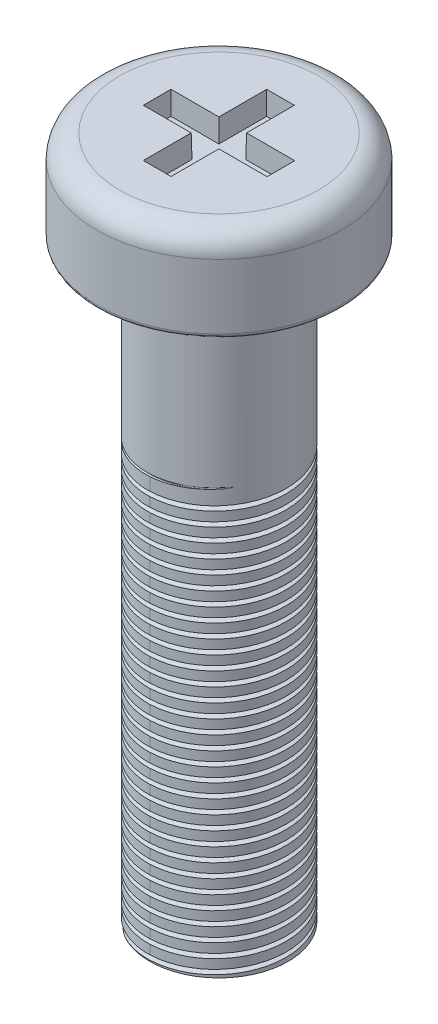
SolidWorks part; units mm, degrees
ref_plane "Front Plane" through (0, 0, 0) normal (0, 0, 1) x (1, 0, 0)
ref_plane "Top Plane" through (0, 0, 0) normal (0, 1, 0) x (1, 0, 0)
ref_plane "Right Plane" through (0, 0, 0) normal (1, 0, 0) x (0, 0, -1)
sketch "Sketch1" plane through (0, 0, 0) normal (0, 1, 0) x (1, 0, 0)
  circle A0 centre (0, 0) radius 2.65
  dimension "D1" = 5.3
extrude "Boss-Extrude1" add sketch "Sketch1" along normal blind 2
sketch "Sketch2" plane through (0, 0, 0) normal (0, -1, 0) x (1, 0, 0)
  circle A0 centre (0, 0) radius 1.5
  dimension "D1" = 3
extrude "Boss-Extrude2" add sketch "Sketch2" along normal blind 12.8
fillet "Fillet1" radius 0.5 1 edges at (0, 2, 2.65)
fillet "Fillet2" radius 0.1 1 edges at (0, 0, 2.65)
sketch "Sketch3" plane through (0, 2, 0) normal (0, 1, 0) x (1, 0, 0)
  line L0 (0.2966, 0.3) -> (1.3407, 0.3)
  line L1 (-1.3407, -0.3) -> (-0.3034, -0.3)
  line L2 (-1.3407, -0.3) -> (-1.3407, 0.3)
  line L3 (-1.3407, 0.3) -> (-0.3034, 0.3)
  line L4 (1.3407, -0.3) -> (1.3407, 0.3)
  line L5 (0.2966, 0.3) -> (0.2966, 1.3361)
  line L6 (-1.3472, 0.3015) -> (-1.3407, 0.3) construction
  line L7 (-0.3034, -1.3361) -> (0.2966, -1.3361)
  line L8 (-0.3034, -1.3361) -> (-0.3034, -0.3)
  line L9 (-0.3034, 1.3361) -> (0.2966, 1.3361)
  line L10 (0.2966, -1.3361) -> (0.2966, -0.3)
  line L11 (-0.0036, -0.0008) -> (-0.0033, 0.0007) construction
  line L12 (-0.0033, 0.0007) -> (-0.003, -0.0007) construction
  line L13 (-0.3034, 0.3) -> (-0.3034, 1.3361)
  line L15 (0.2966, -0.3) -> (1.3407, -0.3)
  line L17 (-0.0036, -0.0008) -> (0, 0) construction
  line L18 (-0.0033, 0.0007) -> (0, 0) construction
  point P0 (0, 0)
  point P6 (-0.0033, 0.0007)
  dimension "D1" = 0.6
  dimension "D2" = 0.6
extrude "Cut-Extrude1" cut sketch "Sketch3" against normal blind 0.5 draft 1
sketch "Sketch4" plane through (0, -12.8, 0) normal (0, -1, 0) x (1, 0, 0)
  circle A1 centre (0, 0) radius 1.5
  circle A2 centre (0, 0) radius 1.5
  dimension "D1" = 0
curve "Helix/Spiral1" pitch 0.3 height 9 turns 30
sketch "Sketch5" plane through (0, 0, 0) normal (0, 0, 1) x (1, 0, 0)
  line L0 (-1.5, -12.85) -> (-1.5, -12.75)
  line L2 (-1.5, 0) -> (-1.5, -12.8) construction
  line L3 (-1.5, -12.75) -> (-1.3951, -12.7858)
  line L4 (-1.5, -12.8) -> (1.5, -12.8) construction
  line L5 (-1.3951, -12.8142) -> (-1.5, -12.85)
  arc A0 (-1.3951, -12.8142) -> (-1.3951, -12.7858) centre (-1.3999, -12.8) ccw
  point P8 (-1.5, -12.8)
  dimension "D1" = 0.1
sweep "Cut-Sweep1" cut profiles "Sketch5" path "Helix/Spiral1" align with end faces yes
ref_plane "Plane1" through (0, -3.8, 0) normal (0, -1, 0) x (-1, 0, 0)
sketch "Sketch6" plane through (0, -3.8, 0) normal (0, -1, 0) x (-1, 0, 0)
  circle A0 centre (0, 0) radius 1.5 construction
  circle A1 centre (0, 0) radius 1.5
sketch "Sketch7" plane through (0, 0, 0) normal (0, 0, -1) x (-1, 0, 0)
  line L1 (1.5026, -3.7491) -> (1.5026, -3.8509)
  line L3 (1.3951, -3.8142) -> (1.5, -3.85)
  line L4 (1.5, -3.85) -> (1.5, -3.75)
  line L5 (1.5, -3.75) -> (1.3951, -3.7858)
  line L6 (1.3951, -3.8142) -> (1.5026, -3.8509)
  line L8 (1.5026, -3.7491) -> (1.3951, -3.7858)
  arc A1 (1.3951, -3.7858) -> (1.3951, -3.8142) centre (1.3999, -3.8) ccw
  arc A2 (1.3951, -3.7858) -> (1.3951, -3.8142) centre (1.3999, -3.8) ccw
  dimension "D1" = 0
curve "Helix/Spiral2"
sweep "Cut-Sweep2" cut profiles "Sketch7" path "Helix/Spiral2"
